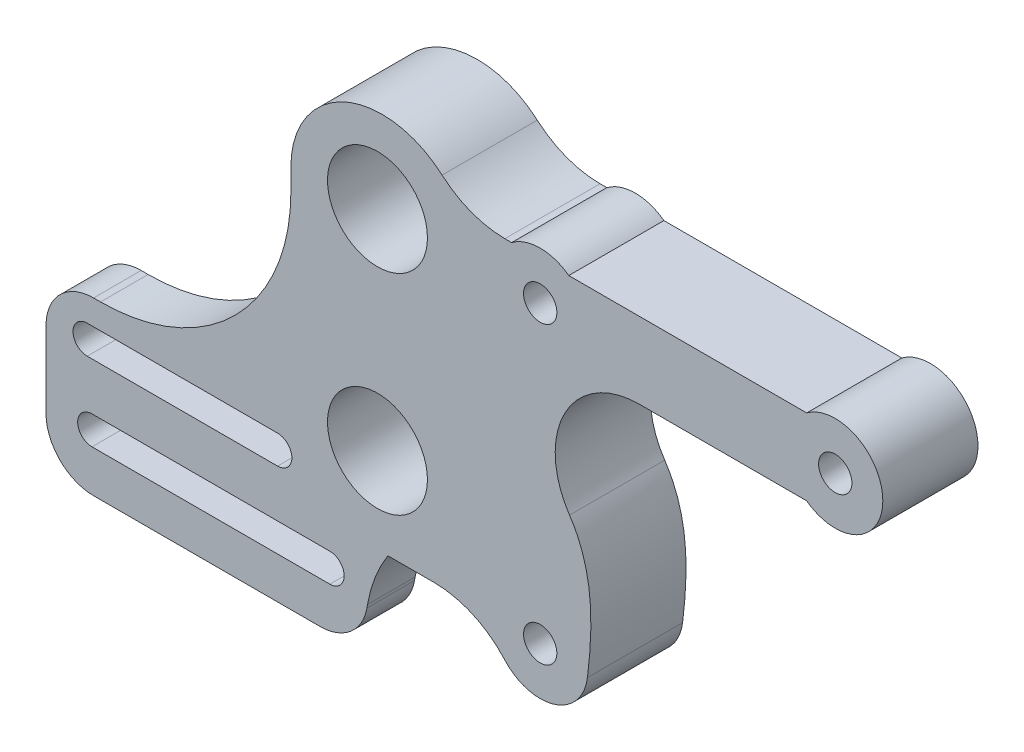
SolidWorks part; units mm, degrees
material "ABS generico"
ref_plane "Piano frontale" through (0, 0, 0) normal (0, 0, 1) x (1, 0, 0)
ref_plane "Piano superiore" through (0, 0, 0) normal (0, 1, 0) x (1, 0, 0)
ref_plane "Piano destro" through (0, 0, 0) normal (1, 0, 0) x (0, 0, -1)
sketch "Sketch1" plane through (0, 0, 0) normal (0, 0, 1) x (1, 0, 0)
  line L0 (59.1153, 43.5513) -> (59.8228, 43.5513)
  line L1 (65.8228, 43.5513) -> (90.8228, 43.5513)
  line L2 (36.6269, 38.8486) -> (36.6269, 18.7513)
  line L3 (51.6425, 8.5513) -> (46.8269, 8.5513)
  line L4 (90.8228, 35.5513) -> (73.2211, 35.5513)
  line L6 (62.8228, -5.7466) -> (62.8228, 55.7339) construction
  line L7 (10.2847, 39.5513) -> (106.4029, 39.5513) construction
  arc A0 (59.096, 5.2179) -> (65.7153, 4.4728) centre (62.8228, 8.5513) ccw
  arc A1 (90.8228, 35.5513) -> (90.8228, 43.5513) centre (93.8228, 39.5513) ccw
  arc A2 (52.5151, 46.0388) -> (36.6269, 38.8486) centre (46.198, 38.8486) ccw
  arc A3 (46.8269, 8.5513) -> (36.6269, 18.7513) centre (46.8269, 18.7513) cw
  arc A4 (73.2211, 35.5513) -> (65.9057, 21.7942) centre (73.2211, 26.7278) ccw
  circle A5 centre (93.8228, 39.5513) radius 1.75
  circle A6 centre (62.8228, 39.5513) radius 1.75
  circle A7 centre (62.8228, 8.5513) radius 1.75
  arc A8 (65.8228, 43.5513) -> (59.8228, 43.5513) centre (62.8228, 39.5513) ccw
  arc A10 (65.7153, 4.4728) -> (67.786, 7.9453) centre (62.8228, 8.5513) ccw
  arc A11 (59.096, 5.2179) -> (51.6425, 8.5513) centre (51.6425, -1.4487) ccw
  arc A12 (59.1153, 43.5513) -> (52.5151, 46.0388) centre (59.1153, 53.5513) cw
  circle A13 centre (45.7251, 39.5513) radius 5.25
  circle A14 centre (45.7251, 17.5513) radius 5.25
  spline S0 degree 3 poles (65.9057, 21.7942) (68.5106, 17.9318) (68.3976, 12.9554) (67.786, 7.9453) knots 0 0 0 0 1 1 1 1
  point P21 (45.7251, 39.5513)
  point P22 (45.7251, 17.5513)
  point P41 (57.8228, 8.5513)
  dimension "D2" = 31
  dimension "D4" = 10
  dimension "D5" = 10
  dimension "D6" = 10.2
  dimension "D7" = 8
  dimension "D8" = 10
  dimension "D9" = 5
  dimension "D10" = 10
  dimension "D11" = 10
  dimension "D12" = 10.5
  dimension "D13" = 3.5
  dimension "D1" = 22
  dimension "D3" = 31
extrude "Boss-Extrude1" add sketch "Sketch1" against normal blind 10
sketch "Sketch2" plane through (0, 0, 0) normal (0, 0, 1) x (1, 0, 0)
  line L0 (45.6366, 8.5513) -> (43.8969, -1.4487)
  line L1 (37.3666, 16.5513) -> (39.364, 12.2499)
  line L2 (37.3666, 16.5513) -> (10.8969, 16.5513)
  line L3 (45.6366, 10.8576) -> (45.6366, 8.5513)
  line L5 (43.8969, -1.4487) -> (10.8969, -1.4487)
  line L9 (10.8969, 16.5513) -> (10.8969, -1.4487)
  line L14 (39.364, 12.2499) -> (45.6366, 10.8576)
  point P0 (49.8144, 8.5513)
  point P1 (-4.8939, 8.5513)
  point P4 (49.8144, 16.5513)
  point P5 (-4.8939, 16.5513)
  point P11 (45.6366, 16.5513)
  point P12 (45.6366, 5.6789)
  point P14 (-4.3634, 5.6789)
  dimension "D2" = 18
  dimension "D1" = 33
extrude "Extrude1" add sketch "Sketch2" against normal blind 5
fillet "Fillet2" radius 20 1 edges at (36.867, 16.5513, -2.5)
fillet "Fillet3" radius 5 1 edges at (10.8969, 16.5513, -2.5)
fillet "Fillet5" radius 5 1 edges at (10.8969, -1.4487, -2.5)
sketch "Sketch3" plane through (0, 0, -5) normal (0, 0, -1) x (-1, 0, 0)
  line L0 (-37.1999, 8.4181) -> (8.3883, 8.4181) construction
  line L1 (-40.7251, 15.9505) -> (-40.7251, -8.1457) construction
  line L2 (-37.1999, 4.4181) -> (8.3883, 4.4181) construction
  line L3 (-37.1999, 12.4181) -> (8.3883, 12.4181) construction
  line L4 (-15.2308, 12.4181) -> (-35.2308, 12.4181) construction
  line L5 (-15.2308, 10.9181) -> (-35.2308, 10.9181)
  line L6 (-15.2308, 13.9181) -> (-35.2308, 13.9181)
  line L7 (-15.7251, 4.4181) -> (-40.7251, 4.4181) construction
  line L8 (-15.7251, 2.9181) -> (-40.7251, 2.9181)
  line L9 (-15.7251, 5.9181) -> (-40.7251, 5.9181)
  arc A0 (-15.2308, 10.9181) -> (-15.2308, 13.9181) centre (-15.2308, 12.4181) ccw
  arc A1 (-35.2308, 13.9181) -> (-35.2308, 10.9181) centre (-35.2308, 12.4181) ccw
  arc A2 (-15.7251, 2.9181) -> (-15.7251, 5.9181) centre (-15.7251, 4.4181) ccw
  arc A3 (-40.7251, 5.9181) -> (-40.7251, 2.9181) centre (-40.7251, 4.4181) ccw
  circle A4 centre (-45.7251, 17.5513) radius 5.25 construction
  point P8 (-25.2308, 12.4181)
  point P14 (-28.2251, 4.4181)
  dimension "D1" = 20
  dimension "D2" = 25
extrude "Extrude2" cut sketch "Sketch3" against normal blind 5
fillet "Fillet7" radius 475 1 edges at (45.6366, 8.621, -2.5)
fillet "Fillet8" radius 15 1 edges at (45.6366, 8.5513, -2.5)
fillet "Fillet9" radius 5 1 edges at (43.8969, -1.4487, -2.5)
sketch "Sketch4" plane through (0, 0, -10) normal (0, 0, -1) x (-1, 0, 0)
  circle A0 centre (-62.8228, 39.5513) radius 3.5
  circle A1 centre (-93.8228, 39.5513) radius 3.5
  circle A2 centre (-62.8228, 8.5513) radius 3.5
  dimension "D1" = 7
  dimension "D2" = 2
  dimension "D3" = 2
extrude "Extrude3" cut sketch "Sketch4" against normal blind 2
